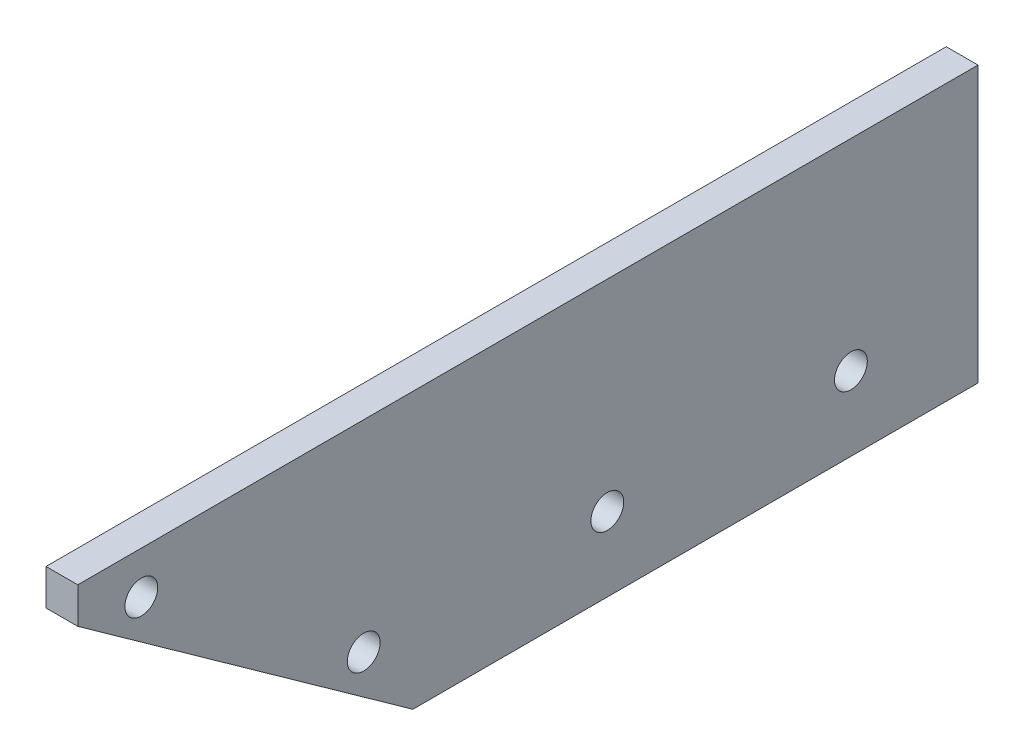
SolidWorks part; units mm, degrees
ref_plane "Ebene vorne" through (0, 0, 0) normal (0, 0, 1) x (1, 0, 0)
ref_plane "Ebene oben" through (0, 0, 0) normal (0, 1, 0) x (1, 0, 0)
ref_plane "Ebene rechts" through (0, 0, 0) normal (1, 0, 0) x (0, 0, -1)
sketch "Skizze1" plane through (0, 0, 0) normal (1, 0, 0) x (0, 0, -1)
  line L1 (0, 0) -> (85, 0)
  line L2 (0, 0) -> (0, 26)
  line L3 (0, 26) -> (85, 26)
  line L4 (85, 0) -> (85, 26)
  dimension "D1" = 85
  dimension "D2" = 26
extrude "Aufsatz-Linear austragen1" add sketch "Skizze1" along normal blind 3
sketch "Skizze2" plane through (3, 0, 0) normal (1, 0, 0) x (0, 0, -1)
  line L0 (6, 0) -> (6, 22) construction
  line L1 (0, 0) -> (85, 0) construction
  line L2 (27, 0) -> (27, 7) construction
  line L3 (50, 0) -> (50, 7) construction
  line L4 (73, 0) -> (73, 7) construction
  line L5 (73, 7) -> (50, 7) construction
  line L6 (50, 7) -> (27, 7) construction
  line L7 (0, 26) -> (0, 0) construction
  circle A0 centre (6, 22) radius 1.55
  circle A1 centre (27, 7) radius 1.55
  circle A2 centre (50, 7) radius 1.55
  circle A3 centre (73, 7) radius 1.55
  dimension "D6" = 3.1
  dimension "D1" = 21
  dimension "D2" = 23
  dimension "D3" = 15
  dimension "D4" = 7
  dimension "D5" = 6
extrude "Schnitt-Linear austragen1" cut sketch "Skizze2" against normal through all
sketch "Skizze3" plane through (3, 0, 0) normal (1, 0, 0) x (0, 0, -1)
  line L0 (0, 22.599) -> (31.6386, 0)
  line L1 (0, 26) -> (0, 0) construction
  line L2 (0, 0) -> (85, 0) construction
  line L3 (31.6386, 0) -> (0, 0)
  line L4 (0, 0) -> (0, 22.599)
  line L5 (6, 22) -> (27, 7) construction
  dimension "D1" = 3
extrude "Schnitt-Linear austragen2" cut sketch "Skizze3" against normal through all
